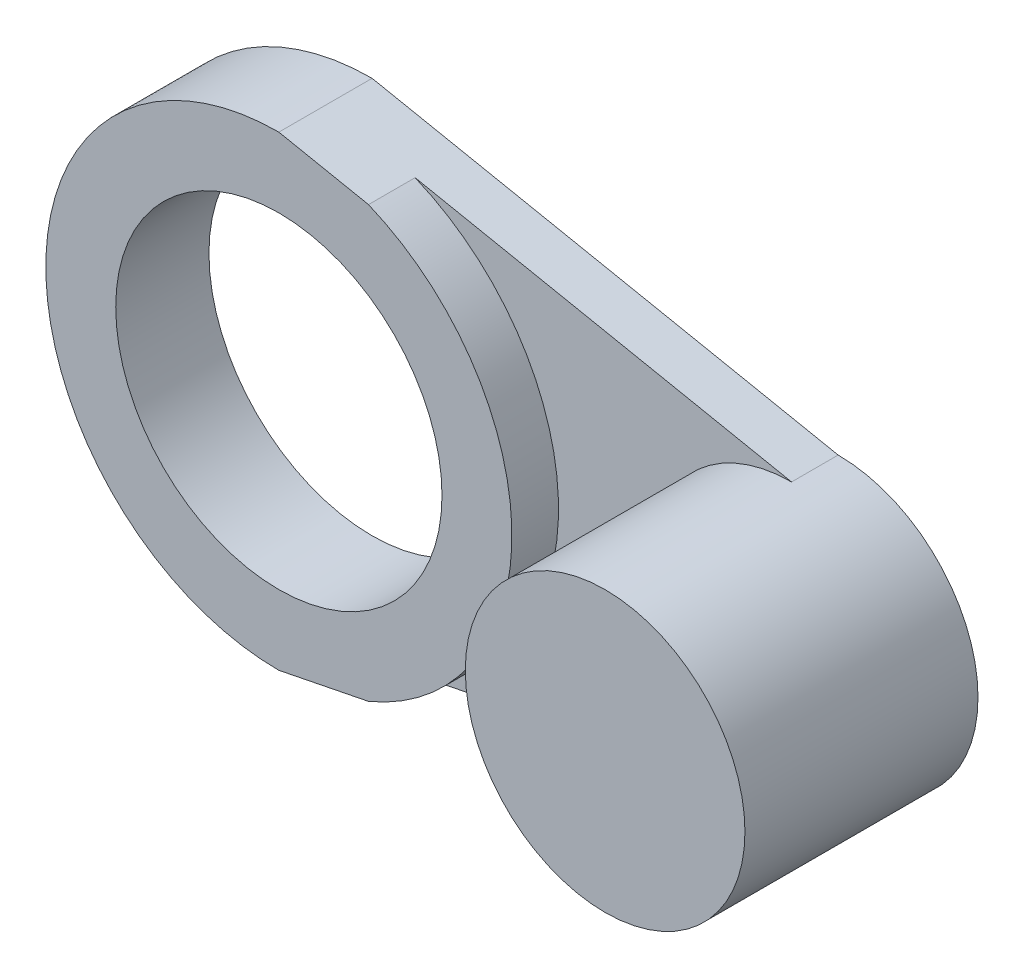
SolidWorks part; units mm, degrees
material "Plain Carbon Steel"
ref_plane "Front Plane" through (0, 0, 0) normal (0, 0, 1) x (1, 0, 0)
ref_plane "Top Plane" through (0, 0, 0) normal (0, 1, 0) x (1, 0, 0)
ref_plane "Right Plane" through (0, 0, 0) normal (1, 0, 0) x (0, 0, -1)
sketch "Sketch1" plane through (0, 0, 0) normal (0, 0, 1) x (1, 0, 0)
  line L0 (0, 25) -> (50, 15)
  line L1 (0, -25) -> (50, -15)
  circle A0 centre (0, 0) radius 25
  circle A1 centre (50, 0) radius 15
  circle A2 centre (0, 0) radius 17.5
  dimension "D1" = 30
  dimension "D2" = 50
  dimension "D4" = 35
  dimension "D3" = 50
extrude "Boss-Extrude1" add sketch "Sketch1" against normal blind 5 contours A1 L0 A0 L1 region at (29.8369, 0, 0)
extrude "Boss-Extrude2" add sketch "Sketch1<3>" along normal blind 20 and the other way blind 5 contours A1 region at (50, 0, 0)
sketch "Sketch1<3>" plane through (0, 0, 0) normal (0, 0, 1) x (1, 0, 0) same geometry as "Sketch1"
extrude "Boss-Extrude3" add sketch "Sketch1<4>" along normal blind 5 and the other way blind 5 contours L0 A0 L1 A2 region at (4.669, 23.3451, 0)
sketch "Sketch1<4>" plane through (0, 0, 0) normal (0, 0, 1) x (1, 0, 0) same geometry as "Sketch1"
